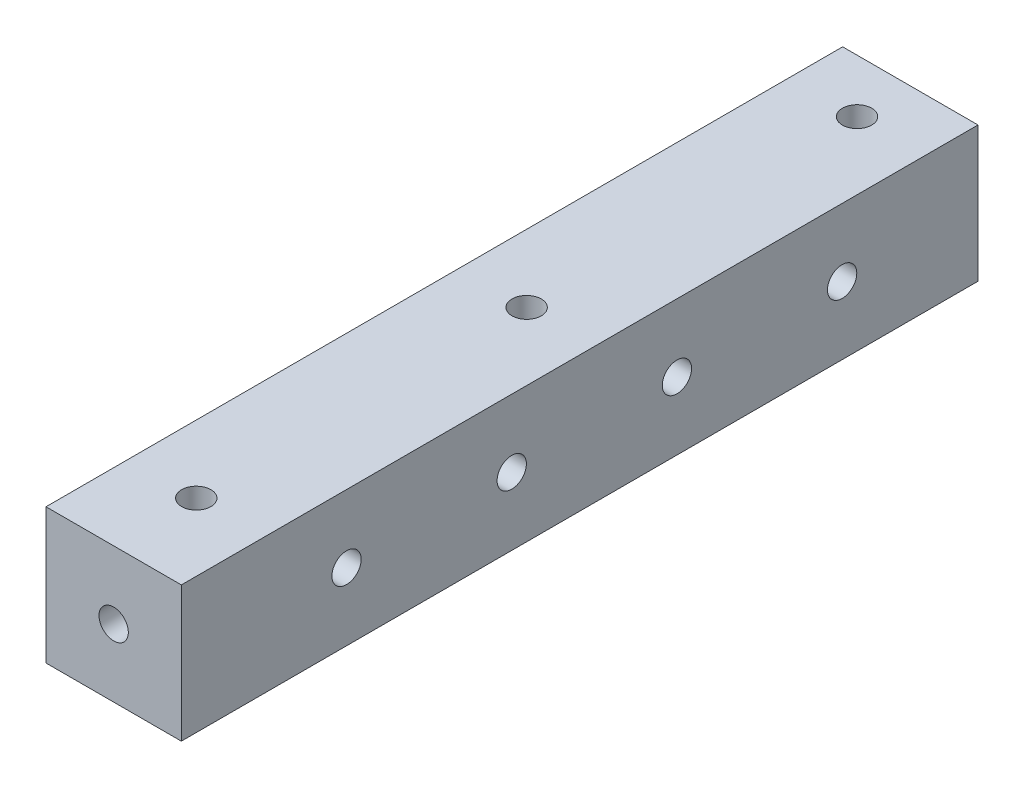
SolidWorks part; units mm, degrees
material "6061 Alloy"
ref_plane "Front Plane" through (0, 0, 0) normal (0, 0, 1) x (1, 0, 0)
ref_plane "Top Plane" through (0, 0, 0) normal (0, 1, 0) x (1, 0, 0)
ref_plane "Right Plane" through (0, 0, 0) normal (1, 0, 0) x (0, 0, -1)
sketch "Sketch1" plane through (0, 0, 0) normal (0, 0, 1) x (1, 0, 0)
  line L1 (-12.7, -12.7) -> (12.7, -12.7)
  line L2 (-12.7, -12.7) -> (-12.7, 12.7)
  line L3 (-12.7, 12.7) -> (12.7, 12.7)
  line L4 (12.7, -12.7) -> (12.7, 12.7)
  line L5 (-12.7, -12.7) -> (12.7, 12.7) construction
  line L6 (-12.7, 12.7) -> (12.7, -12.7) construction
  point P0 (0, 0)
  dimension "D1" = 25.4
extrude "Boss-Extrude1" add sketch "Sketch1" along normal mid plane 155
sketch "Sketch2" plane through (0, 0, 77.5) normal (0, 0, 1) x (1, 0, 0)
  point P0 (0, 0)
sketch "Sketch4" plane through (12.7, 0, 0) normal (1, 0, 0) x (0, 0, -1)
  line L0 (-77.5, -12.7) -> (-77.5, 12.7) construction
  point P0 (-46.5, 0)
  point P1 (-15.5, 0)
  point P2 (15.5, 0)
  point P3 (46.5, 0)
  dimension "D1" = 31
  dimension "D2" = 31
  dimension "D3" = 31
  dimension "D4" = 31
sketch "Sketch5" plane through (0, -12.7, 0) normal (0, -1, 0) x (1, 0, 0)
  line L0 (-12.7, 77.5) -> (12.7, 77.5) construction
  line L1 (-12.7, -77.5) -> (12.7, -77.5) construction
  point P0 (0, 62)
  point P1 (0, 0)
  point P2 (0, -62)
  dimension "D1" = 15.5
  dimension "D2" = 15.5
hole_wizard "M5 Clearance Hole1" positions "Sketch6" profile "Sketch8" hole size "M5" standard "ANSI Metric" end condition through all
sketch "Sketch6" plane through (12.7, 0, 0) normal (1, 0, 0) x (0, 0, -1)
  point P0 (-46.5, 0)
  point P3 (-15.5, 0)
  point P6 (15.5, 0)
  point P9 (46.5, 0)
sketch "Sketch8" plane through (12.7, 0, 46.5) normal (0, 1, 0) x (0, 0, -1)
  line L0 (0, 0) -> (0, 25.4)
  line L1 (0, 25.4) -> (2.75, 25.4)
  line L2 (2.75, 25.4) -> (2.75, 0)
  line L5 (2.75, 0) -> (0, 0)
  line L11 (0, -6.35) -> (0, 107.95) construction
  dimension "Thru Hole Dia." = 5.5
  dimension "Thru Hole Depth" = 25.4
hole_wizard "M5 Clearance Hole2" positions "Sketch9" profile "Sketch10" hole size "M5" standard "ANSI Metric" end condition through all
sketch "Sketch9" plane through (0, -12.7, 0) normal (0, -1, 0) x (-1, 0, 0)
  point P0 (0, -62)
  point P3 (0, 0)
  point P6 (0, 62)
sketch "Sketch10" plane through (0, -12.7, 62) normal (1, 0, 0) x (0, 0, -1)
  line L0 (0, 0) -> (0, 25.4)
  line L1 (0, 25.4) -> (2.75, 25.4)
  line L2 (2.75, 25.4) -> (2.75, 0)
  line L5 (2.75, 0) -> (0, 0)
  line L11 (0, -6.35) -> (0, 107.95) construction
  dimension "Thru Hole Dia." = 5.5
  dimension "Thru Hole Depth" = 25.4
hole_wizard "M5 Clearance Hole3" positions "Sketch11" profile "Sketch12" hole size "M5" standard "ANSI Metric"
sketch "Sketch11" plane through (0, 0, 77.5) normal (0, 0, 1) x (1, 0, 0)
  point P0 (0, 0)
sketch "Sketch12" plane through (0, 0, 77.5) normal (1, 0, 0) x (0, -1, 0)
  line L0 (0, 0) -> (0, 11.6524)
  line L1 (0, 11.6524) -> (2.75, 10)
  line L2 (2.75, 10) -> (2.75, 0)
  line L5 (2.75, 0) -> (0, 0)
  line L10 (0, 11.6524) -> (-2.75, 10) construction
  line L11 (0, -6.35) -> (0, 107.95) construction
  dimension "Hole Dia." = 5.5
  dimension "Hole Depth" = 10
  dimension "Drill Angle" = 118
sketch "Sketch13" plane through (0, 12.7, 0) normal (0, 1, 0) x (1, 0, 0)
  line L0 (12.7, -77.5) -> (12.7, 77.5) construction
  line L1 (12.7, 72) -> (-12.7, 72)
  line L2 (12.7, 72) -> (12.7, 77.5)
  line L3 (12.7, 77.5) -> (-12.7, 77.5)
  line L4 (-12.7, 72) -> (-12.7, 77.5)
  line L5 (-12.7, -77.5) -> (-12.7, 77.5) construction
  line L6 (12.7, 77.5) -> (-12.7, 77.5) construction
  circle A0 centre (0, 62) radius 2.75 construction
  dimension "D1" = 10
extrude "Cut-Extrude1" cut sketch "Sketch13" against normal through all
